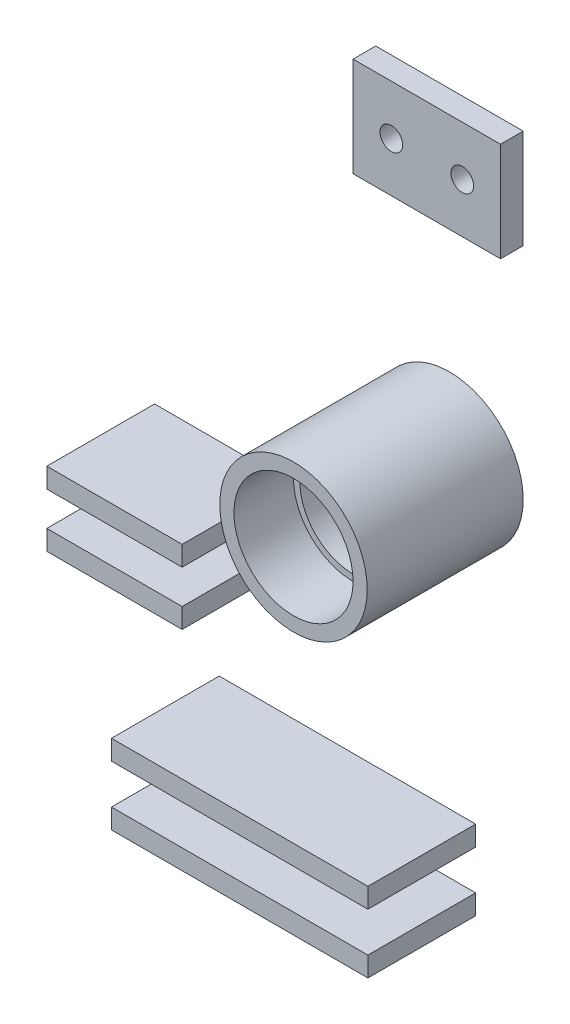
SolidWorks part; units mm, degrees
ref_plane "Front Plane" through (0, 0, 0) normal (0, 0, 1) x (1, 0, 0)
ref_plane "Top Plane" through (0, 0, 0) normal (0, 1, 0) x (1, 0, 0)
ref_plane "Right Plane" through (0, 0, 0) normal (1, 0, 0) x (0, 0, -1)
sketch "Sketch2" plane through (0, 0, 0) normal (0, 0, 1) x (1, 0, 0)
  circle A0 centre (0, 0) radius 26
  dimension "D1" = 52
extrude "Boss-Extrude1" add sketch "Sketch2" along normal blind 55
sketch "Sketch3" plane through (0, 0, 55) normal (0, 0, 1) x (1, 0, 0)
  circle A0 centre (0, 0) radius 18.75
  dimension "D1" = 37.5
extrude "Cut-Extrude1" cut sketch "Sketch3" against normal up to surface (55 mm away) up to face at (26, 0, 0)
sketch "Sketch4" plane through (0, 0, 55) normal (0, 0, 1) x (1, 0, 0)
  circle A0 centre (0, 0) radius 21
  dimension "D1" = 42
extrude "Cut-Extrude2" cut sketch "Sketch4" against normal blind 21
sketch "Sketch5" plane through (0, 0, 0) normal (0, 0, -1) x (-1, 0, 0)
  circle A0 centre (0, 0) radius 23.5
  dimension "D1" = 47
extrude "Cut-Extrude3" cut sketch "Sketch5" against normal blind 15
sketch "Sketch6" plane through (0, 0, 0) normal (0, 0, -1) x (-1, 0, 0)
  circle A0 centre (0, 0) radius 21
  dimension "D1" = 42
extrude "Cut-Extrude4" cut sketch "Sketch6" against normal blind 25
ref_plane "UBJ Point Plane" through (0, 0, 45) normal (0, 0, -1) x (-1, 0, 0)
ref_plane "LBJ Point Plane" through (0, 0, 38.35) normal (0, 0, -1) x (-1, 0, 0)
ref_plane "Tie Rod Point Plane" through (0, 0, 25.65) normal (0, 0, -1) x (-1, 0, 0)
sketch "Sketch7" plane through (0, 0, 45) normal (0, 0, -1) x (-1, 0, 0)
  point P0 (0, 95)
  point P1 (0, 95)
  dimension "D1" = 95
ref_point "UBJ Point"
sketch "Sketch8" plane through (0, 0, 38.35) normal (0, 0, -1) x (-1, 0, 0)
  point P0 (9.98, -95.5)
  dimension "D1" = 190.5
  dimension "D2" = 9.98
ref_point "LBJ Point"
sketch "Sketch9" plane through (0, 0, 25.65) normal (0, 0, -1) x (-1, 0, 0)
  point P0 (73.48, -42.16)
  dimension "D1" = 63.5
  dimension "D2" = 53.34
ref_point "Tie Rod Point"
sketch "Sketch10" plane through (0, 0, 0) normal (0, 0, 1) x (1, 0, 0)
  line L0 (-12.5, 95) -> (12.5, 95) construction
  line L1 (-26, 112.5) -> (26, 112.5)
  line L2 (-26, 112.5) -> (-26, 77.5)
  line L3 (-26, 77.5) -> (26, 77.5)
  line L4 (26, 112.5) -> (26, 77.5)
  line L5 (-26, 112.5) -> (26, 77.5) construction
  line L6 (-26, 77.5) -> (26, 112.5) construction
  circle A0 centre (0, 0) radius 26 construction
  circle A1 centre (-12.5, 95) radius 4
  circle A2 centre (12.5, 95) radius 4
  point P0 (0, 95)
  point P7 (0, 95)
  dimension "D2" = 8
  dimension "D1" = 35
  dimension "D3" = 25
extrude "Boss-Extrude2" add sketch "Sketch10" along normal blind 8 separate body contours L1 L4 L3 L2
sketch "Sketch12" plane through (0, 0, 0) normal (0, 0, 1) x (1, 0, 0)
  line L0 (-12.5, 95) -> (12.5, 95) construction
  circle A0 centre (-12.5, 95) radius 4
  circle A1 centre (12.5, 95) radius 4
  point P4 (-15.1527, 87.6656)
  dimension "D1" = 8
  dimension "D2" = 25
extrude "Cut-Extrude5" cut sketch "Sketch12" along normal up to surface (8 mm away) up to face at (0, 95, 8)
sketch "Sketch13" plane through (0, 0, 45) normal (0, 0, -1) x (-1, 0, 0)
  line L0 (9.98, -85) -> (9.98, -106) construction
  line L1 (55.1948, -88.5) -> (-35.2348, -88.5)
  line L2 (55.1948, -88.5) -> (55.1948, -81.5)
  line L3 (55.1948, -81.5) -> (-35.2348, -81.5)
  line L4 (-35.2348, -88.5) -> (-35.2348, -81.5)
  line L5 (55.1948, -88.5) -> (-35.2348, -81.5) construction
  line L6 (55.1948, -81.5) -> (-35.2348, -88.5) construction
  line L7 (55.1948, -109.5) -> (-35.2348, -109.5)
  line L8 (55.1948, -109.5) -> (55.1948, -102.5)
  line L9 (55.1948, -102.5) -> (-35.2348, -102.5)
  line L10 (-35.2348, -109.5) -> (-35.2348, -102.5)
  line L11 (55.1948, -109.5) -> (-35.2348, -102.5) construction
  line L12 (55.1948, -102.5) -> (-35.2348, -109.5) construction
  point P0 (9.98, -85)
  point P5 (9.98, -106)
  point P10 (-72.1179, -88.5)
  point P12 (-22.0922, -81.5)
  point P13 (-35.2348, -81.5)
  dimension "D1" = 7
  dimension "D2" = 7
extrude "Boss-Extrude3" add sketch "Sketch13" along normal mid plane 38 separate body
sketch "Sketch14" plane through (0, 0, 25.65) normal (0, 0, -1) x (-1, 0, 0)
  line L0 (73.48, -42.16) -> (73.48, -32.66) construction
  line L1 (97.3439, -36.16) -> (49.6161, -36.16)
  line L2 (97.3439, -36.16) -> (97.3439, -29.16)
  line L3 (97.3439, -29.16) -> (49.6161, -29.16)
  line L4 (49.6161, -36.16) -> (49.6161, -29.16)
  line L5 (97.3439, -36.16) -> (49.6161, -29.16) construction
  line L6 (97.3439, -29.16) -> (49.6161, -36.16) construction
  line L7 (87.3597, -42.16) -> (61.8488, -42.16) construction
  line L8 (73.48, -42.16) -> (73.48, -51.66) construction
  line L9 (49.6161, -48.16) -> (49.6161, -55.16)
  line L10 (97.3439, -48.16) -> (97.3439, -55.16)
  line L11 (97.3439, -48.16) -> (49.6161, -48.16)
  line L12 (97.3439, -48.16) -> (49.6161, -55.16) construction
  line L13 (97.3439, -55.16) -> (49.6161, -48.16) construction
  line L14 (97.3439, -55.16) -> (49.6161, -55.16)
  point P0 (73.48, -32.66)
  point P11 (73.48, -51.66)
  point P16 (97.3439, -36.16)
  point P17 (0, 0)
  point P18 (97.3025, -35.0874)
  dimension "D1" = 7
  dimension "D2" = 6
extrude "Boss-Extrude4" add sketch "Sketch14" along normal mid plane 38 separate body contours L3 L4 L1 L2 | L14 L9 L11 L10
